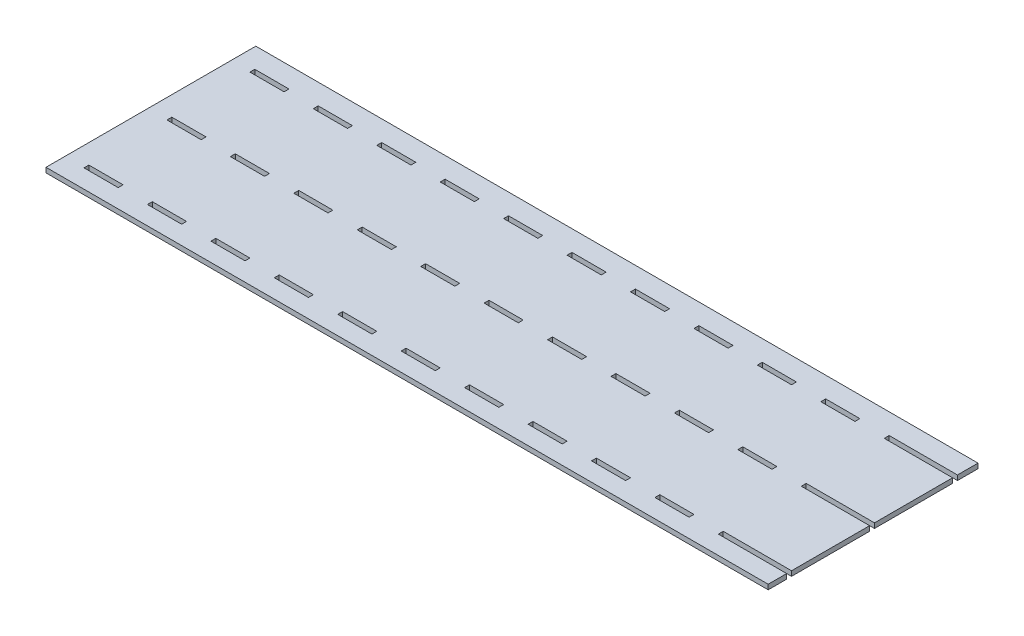
SolidWorks part; units mm, degrees
material "Balsa"
ref_plane "Front Plane" through (0, 0, 0) normal (0, 0, 1) x (1, 0, 0)
ref_plane "Top Plane" through (0, 0, 0) normal (0, 1, 0) x (1, 0, 0)
ref_plane "Right Plane" through (0, 0, 0) normal (1, 0, 0) x (0, 0, -1)
sketch "Sketch1" plane through (0, 0, 0) normal (0, 1, 0) x (1, 0, 0)
  line L0 (0, 0) -> (0, -273.05)
  line L1 (0, -273.05) -> (939.8, -273.05)
  line L2 (939.8, -273.05) -> (939.8, 0)
  line L3 (939.8, 0) -> (0, 0)
extrude "Boss-Extrude1" add sketch "Sketch1" along normal blind 6.35
sketch "Sketch2" plane through (0, 6.35, 0) normal (0, 1, 0) x (1, 0, 0)
  line L0 (25.4, -26.7387) -> (69.85, -26.7387)
  line L1 (69.85, -26.7387) -> (69.85, -33.0887)
  line L2 (69.85, -33.0887) -> (25.4, -33.0887)
  line L3 (25.4, -33.0887) -> (25.4, -26.7387)
  line L4 (107.95, -33.0887) -> (107.95, -26.7387)
  line L5 (107.95, -26.7387) -> (152.4, -26.7387)
  line L6 (152.4, -26.7387) -> (152.4, -33.0887)
  line L7 (152.4, -33.0887) -> (107.95, -33.0887)
  line L8 (190.5, -33.0887) -> (190.5, -26.7387)
  line L9 (190.5, -26.7387) -> (234.95, -26.7387)
  line L10 (234.95, -26.7387) -> (234.95, -33.0887)
  line L11 (234.95, -33.0887) -> (190.5, -33.0887)
  line L12 (273.05, -33.0887) -> (273.05, -26.7387)
  line L13 (273.05, -26.7387) -> (317.5, -26.7387)
  line L14 (317.5, -26.7387) -> (317.5, -33.0887)
  line L15 (317.5, -33.0887) -> (273.05, -33.0887)
  line L16 (355.6, -33.0887) -> (355.6, -26.7387)
  line L17 (355.6, -26.7387) -> (400.05, -26.7387)
  line L18 (400.05, -26.7387) -> (400.05, -33.0887)
  line L19 (400.05, -33.0887) -> (355.6, -33.0887)
  line L20 (438.15, -33.0887) -> (438.15, -26.7387)
  line L21 (438.15, -26.7387) -> (482.6, -26.7387)
  line L22 (482.6, -26.7387) -> (482.6, -33.0887)
  line L23 (482.6, -33.0887) -> (438.15, -33.0887)
  line L24 (520.7, -33.0887) -> (520.7, -26.7387)
  line L25 (520.7, -26.7387) -> (565.15, -26.7387)
  line L26 (565.15, -26.7387) -> (565.15, -33.0887)
  line L27 (565.15, -33.0887) -> (520.7, -33.0887)
  line L28 (603.25, -33.0887) -> (603.25, -26.7387)
  line L29 (603.25, -26.7387) -> (647.7, -26.7387)
  line L30 (647.7, -26.7387) -> (647.7, -33.0887)
  line L31 (647.7, -33.0887) -> (603.25, -33.0887)
  line L32 (685.8, -33.0887) -> (685.8, -26.7387)
  line L33 (685.8, -26.7387) -> (730.25, -26.7387)
  line L34 (730.25, -26.7387) -> (730.25, -33.0887)
  line L35 (730.25, -33.0887) -> (685.8, -33.0887)
  line L36 (768.35, -33.0887) -> (768.35, -26.7387)
  line L37 (768.35, -26.7387) -> (812.8, -26.7387)
  line L38 (812.8, -26.7387) -> (812.8, -33.0887)
  line L39 (812.8, -33.0887) -> (768.35, -33.0887)
  line L40 (107.95, -141.0387) -> (107.95, -134.6887)
  line L41 (107.95, -134.6887) -> (152.4, -134.6887)
  line L42 (152.4, -134.6887) -> (152.4, -141.0387)
  line L43 (152.4, -141.0387) -> (107.95, -141.0387)
  line L44 (190.5, -141.0387) -> (190.5, -134.6887)
  line L45 (190.5, -134.6887) -> (234.95, -134.6887)
  line L46 (234.95, -134.6887) -> (234.95, -141.0387)
  line L47 (234.95, -141.0387) -> (190.5, -141.0387)
  line L48 (273.05, -141.0387) -> (273.05, -134.6887)
  line L49 (273.05, -134.6887) -> (317.5, -134.6887)
  line L50 (317.5, -134.6887) -> (317.5, -141.0387)
  line L51 (317.5, -141.0387) -> (273.05, -141.0387)
  line L52 (355.6, -141.0387) -> (355.6, -134.6887)
  line L53 (355.6, -134.6887) -> (400.05, -134.6887)
  line L54 (400.05, -134.6887) -> (400.05, -141.0387)
  line L55 (400.05, -141.0387) -> (355.6, -141.0387)
  line L56 (438.15, -141.0387) -> (438.15, -134.6887)
  line L57 (438.15, -134.6887) -> (482.6, -134.6887)
  line L58 (482.6, -134.6887) -> (482.6, -141.0387)
  line L59 (482.6, -141.0387) -> (438.15, -141.0387)
  line L60 (520.7, -141.0387) -> (520.7, -134.6887)
  line L61 (520.7, -134.6887) -> (565.15, -134.6887)
  line L62 (565.15, -134.6887) -> (565.15, -141.0387)
  line L63 (565.15, -141.0387) -> (520.7, -141.0387)
  line L64 (603.25, -141.0387) -> (603.25, -134.6887)
  line L65 (603.25, -134.6887) -> (647.7, -134.6887)
  line L66 (647.7, -134.6887) -> (647.7, -141.0387)
  line L67 (647.7, -141.0387) -> (603.25, -141.0387)
  line L68 (685.8, -141.0387) -> (685.8, -134.6887)
  line L69 (685.8, -134.6887) -> (730.25, -134.6887)
  line L70 (730.25, -134.6887) -> (730.25, -141.0387)
  line L71 (730.25, -141.0387) -> (685.8, -141.0387)
  line L72 (768.35, -141.0387) -> (768.35, -134.6887)
  line L73 (768.35, -134.6887) -> (812.8, -134.6887)
  line L74 (812.8, -134.6887) -> (812.8, -141.0387)
  line L75 (812.8, -141.0387) -> (768.35, -141.0387)
  line L76 (107.95, -248.9887) -> (107.95, -242.6387)
  line L77 (107.95, -242.6387) -> (152.4, -242.6387)
  line L78 (152.4, -242.6387) -> (152.4, -248.9887)
  line L79 (152.4, -248.9887) -> (107.95, -248.9887)
  line L80 (190.5, -248.9887) -> (190.5, -242.6387)
  line L81 (190.5, -242.6387) -> (234.95, -242.6387)
  line L82 (234.95, -242.6387) -> (234.95, -248.9887)
  line L83 (234.95, -248.9887) -> (190.5, -248.9887)
  line L84 (273.05, -248.9887) -> (273.05, -242.6387)
  line L85 (273.05, -242.6387) -> (317.5, -242.6387)
  line L86 (317.5, -242.6387) -> (317.5, -248.9887)
  line L87 (317.5, -248.9887) -> (273.05, -248.9887)
  line L88 (355.6, -248.9887) -> (355.6, -242.6387)
  line L89 (355.6, -242.6387) -> (400.05, -242.6387)
  line L90 (400.05, -242.6387) -> (400.05, -248.9887)
  line L91 (400.05, -248.9887) -> (355.6, -248.9887)
  line L92 (438.15, -248.9887) -> (438.15, -242.6387)
  line L93 (438.15, -242.6387) -> (482.6, -242.6387)
  line L94 (482.6, -242.6387) -> (482.6, -248.9887)
  line L95 (482.6, -248.9887) -> (438.15, -248.9887)
  line L96 (520.7, -248.9887) -> (520.7, -242.6387)
  line L97 (520.7, -242.6387) -> (565.15, -242.6387)
  line L98 (565.15, -242.6387) -> (565.15, -248.9887)
  line L99 (565.15, -248.9887) -> (520.7, -248.9887)
  line L100 (603.25, -248.9887) -> (603.25, -242.6387)
  line L101 (603.25, -242.6387) -> (647.7, -242.6387)
  line L102 (647.7, -242.6387) -> (647.7, -248.9887)
  line L103 (647.7, -248.9887) -> (603.25, -248.9887)
  line L104 (685.8, -248.9887) -> (685.8, -242.6387)
  line L105 (685.8, -242.6387) -> (730.25, -242.6387)
  line L106 (730.25, -242.6387) -> (730.25, -248.9887)
  line L107 (730.25, -248.9887) -> (685.8, -248.9887)
  line L108 (768.35, -248.9887) -> (768.35, -242.6387)
  line L109 (768.35, -242.6387) -> (812.8, -242.6387)
  line L110 (812.8, -242.6387) -> (812.8, -248.9887)
  line L111 (812.8, -248.9887) -> (768.35, -248.9887)
  line L112 (25.4, -141.0387) -> (25.4, -134.6887)
  line L113 (25.4, -134.6887) -> (69.85, -134.6887)
  line L114 (69.85, -134.6887) -> (69.85, -141.0387)
  line L115 (69.85, -141.0387) -> (25.4, -141.0387)
  line L116 (25.4, -248.9887) -> (25.4, -242.6387)
  line L117 (25.4, -242.6387) -> (69.85, -242.6387)
  line L118 (69.85, -242.6387) -> (69.85, -248.9887)
  line L119 (69.85, -248.9887) -> (25.4, -248.9887)
  line L120 (939.8, -134.6887) -> (850.9, -134.6887)
  line L121 (850.9, -134.6887) -> (850.9, -141.0387)
  line L122 (850.9, -141.0387) -> (939.8, -141.0387)
  line L123 (850.9, -26.7387) -> (850.9, -33.0887)
  line L124 (850.9, -33.0887) -> (939.8, -33.0887)
  line L125 (939.8, -273.05) -> (939.8, 0) construction
  line L126 (939.8, -33.0887) -> (939.8, -26.7387)
  line L127 (939.8, -26.7387) -> (850.9, -26.7387)
  line L128 (939.8, -141.0387) -> (939.8, -134.6887)
  line L129 (939.8, -242.6387) -> (850.9, -242.6387)
  line L130 (850.9, -242.6387) -> (850.9, -248.9887)
  line L131 (850.9, -248.9887) -> (939.8, -248.9887)
  line L132 (939.8, -248.9887) -> (939.8, -242.6387)
  dimension "D1" = 10
  dimension "D3" = 3
  dimension "D2" = 3
extrude "Cut-Extrude1" cut sketch "Sketch2" against normal through all both and the other way through all
